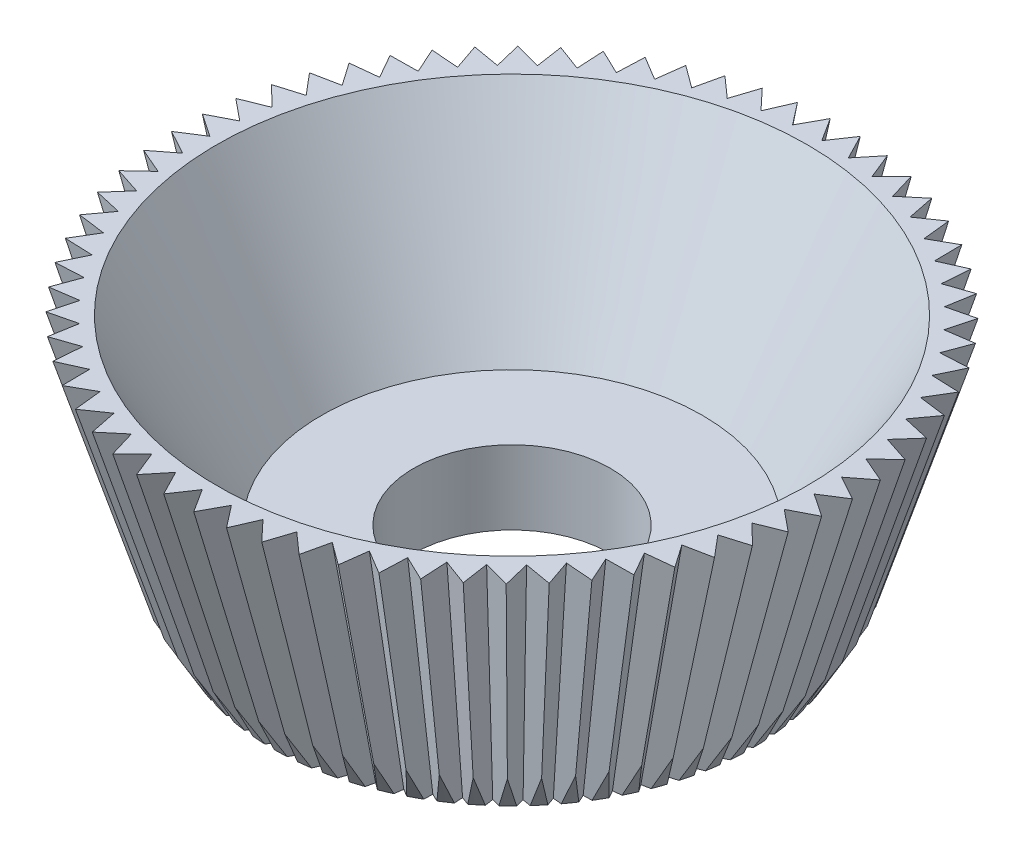
SolidWorks part; units mm, degrees
ref_plane "Front Plane" through (0, 0, 0) normal (0, 0, 1) x (1, 0, 0)
ref_plane "Top Plane" through (0, 0, 0) normal (0, 1, 0) x (1, 0, 0)
ref_plane "Right Plane" through (0, 0, 0) normal (1, 0, 0) x (0, 0, -1)
sketch "Sketch1" plane through (0, 0, 0) normal (0, 0, 1) x (1, 0, 0)
  line L1 (4.867, 9.8055) -> (7, 13.5)
  line L2 (3.867, 11.3055) -> (6, 15)
  line L4 (0, 9.8055) -> (4.867, 9.8055) construction
  line L5 (0, 9.8055) -> (0, 15) construction
  line L6 (4.867, 9.8055) -> (2, 9.8055)
  line L7 (2, 9.8055) -> (2, 11.3055)
  line L8 (2, 11.3055) -> (3.867, 11.3055)
  line L9 (7, 13.5) -> (7, 15)
  line L10 (7, 15) -> (6, 15)
  point P3 (4.867, 9.8055)
  dimension "D1" = 7
  dimension "D2" = 120
  dimension "D3" = 15
  dimension "D4" = 1
  dimension "D5" = 1.5
  dimension "D6" = 1.5
  dimension "D7" = 2
revolve "Revolve1" add sketch "Sketch1" angle 360 about L5
sketch "Sketch2" plane through (0, 15, 0) normal (0, 1, 0) x (1, 0, 0)
  line L0 (0.0575, -6.9998) -> (0.4964, -6.1975)
  line L1 (0.4964, -6.1975) -> (1.0575, -6.9197)
  arc A0 (0.0575, -6.9998) -> (1.0575, -6.9197) centre (0, 0) ccw
  circle A1 centre (0, 0) radius 7 construction
  dimension "D1" = 1
extrude "Cut-Extrude1" cut sketch "Sketch2" against normal through all draft 9 draft outward yes
pattern_circular "CirPattern1" count 68 over 360 about axis through (0, 15, 0) along (0, -1, 0) of "Cut-Extrude1"
sketch "Sketch3" plane through (0, 11.3055, 0) normal (0, 1, 0) x (1, 0, 0)
  line L0 (0, 3.867) -> (0, 2) construction
  circle A0 centre (0, 2.9335) radius 2
  circle A1 centre (0, 0) radius 3.867 construction
  circle A2 centre (0, 0) radius 2 construction
  point P10 (0, 2.9335)
  dimension "D1" = 4
